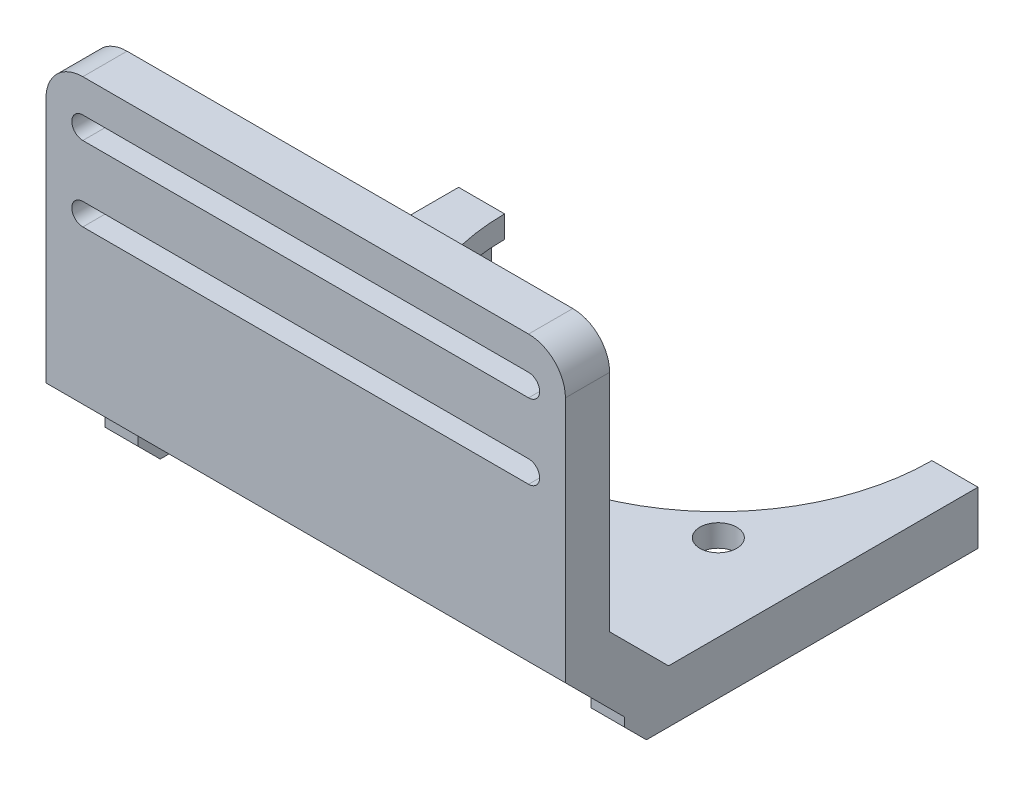
SolidWorks part; units mm, degrees
ref_plane "Front Plane" through (0, 0, 0) normal (0, 0, 1) x (1, 0, 0)
ref_plane "Top Plane" through (0, 0, 0) normal (0, 1, 0) x (1, 0, 0)
ref_plane "Right Plane" through (0, 0, 0) normal (1, 0, 0) x (0, 0, -1)
sketch "Sketch1" plane through (0, 0, 0) normal (0, 0, 1) x (1, 0, 0)
  line L1 (-35.25, 23.25) -> (35.25, 23.25)
  line L2 (-35.25, 23.25) -> (-35.25, -23.25)
  line L3 (-35.25, -23.25) -> (35.25, -23.25)
  line L4 (35.25, 23.25) -> (35.25, -23.25)
  line L5 (-35.25, 23.25) -> (35.25, -23.25) construction
  line L6 (-35.25, -23.25) -> (35.25, 23.25) construction
  point P0 (0, 0)
  dimension "D1" = 70.5
  dimension "D2" = 46.5
extrude "Boss-Extrude1" add sketch "Sketch1" along normal blind 6
sketch "Sketch2" plane through (0, 0, 0) normal (0, 0, -1) x (-1, 0, 0)
  line L0 (35.25, 23.25) -> (35.25, -23.25) construction
  line L1 (-35.25, -23.25) -> (35.25, -23.25)
  line L2 (-35.25, -23.25) -> (-35.25, -20.25)
  line L3 (-35.25, -20.25) -> (35.25, -20.25)
  line L4 (35.25, -23.25) -> (35.25, -20.25)
  dimension "D1" = 3
extrude "Boss-Extrude2" add sketch "Sketch2" along normal blind 50 contours L2 L1 L4 L3
sketch "Sketch3" plane through (0, -20.25, 0) normal (0, 1, 0) x (1, 0, 0)
  line L1 (35.25, 50) -> (-35.25, 50) construction
  circle A1 centre (0, 50) radius 29
  dimension "D1" = 58
extrude "Cut-Extrude1" cut sketch "Sketch3" against normal up to next
sketch "Sketch4" plane through (35.25, 0, 0) normal (1, 0, 0) x (0, 0, -1)
  line L1 (0, -20.25) -> (8, -20.25)
  line L2 (0, -20.25) -> (0, -12.25)
  line L3 (0, -12.25) -> (8, -12.25)
  line L4 (8, -20.25) -> (8, -12.25)
  dimension "D1" = 8
  dimension "D2" = 8
extrude "Boss-Extrude3" add sketch "Sketch4" against normal up to surface (70.5 mm away) up to face at (-35.25, -6.75, -14.6667)
chamfer "Chamfer1" distance 8 angle 45 2 edges at (0, -12.25, -8) (0, -23.25, 6)
sketch "Sketch5" plane through (0, -20.25, 0) normal (0, 1, 0) x (1, 0, 0)
  line L1 (-35.25, 8) -> (35.25, 8) construction
  line L2 (0, 21) -> (0, 8) construction
  line L3 (-29, 50) -> (29, 50) construction
  line L5 (-30.25, 80.25) -> (30.25, 80.25)
  line L6 (-30.25, 80.25) -> (-30.25, 19.75)
  line L7 (-30.25, 19.75) -> (30.25, 19.75)
  line L8 (30.25, 80.25) -> (30.25, 19.75)
  line L9 (-30.25, 80.25) -> (30.25, 19.75) construction
  line L10 (-30.25, 19.75) -> (30.25, 80.25) construction
  circle A0 centre (-23.57, 26.43) radius 2.5
  arc A1 (-29, 50) -> (29, 50) centre (0, 50) ccw construction
  circle A2 centre (23.57, 26.43) radius 2.5
  point P19 (0, 50)
  dimension "D3" = 5
  dimension "D1" = 6.68
  dimension "D2" = 6.68
  dimension "D4" = 60.5
  dimension "D5" = 60.5
extrude "Cut-Extrude2" cut sketch "Sketch5" against normal blind 20 contours A0 | A2
sketch "Sketch6" plane through (0, -23.25, 0) normal (0, -1, 0) x (1, 0, 0)
  line L0 (35.25, -2) -> (-35.25, -2) construction
  line L1 (-35.25, -50) -> (-30.75, -50)
  line L2 (-35.25, -50) -> (-35.25, -2)
  line L3 (-35.25, -2) -> (-30.75, -2)
  line L4 (-30.75, -50) -> (-30.75, -2)
  line L5 (0, 0) -> (0, -21) construction
  line L6 (35.25, -2) -> (30.75, -2)
  line L7 (30.75, -50) -> (30.75, -2)
  line L8 (35.25, -50) -> (30.75, -50)
  line L9 (35.25, -50) -> (35.25, -2)
  arc A0 (29, -50) -> (-29, -50) centre (0, -50) ccw construction
  dimension "D1" = 4.5
extrude "Boss-Extrude4" add sketch "Sketch6" along normal blind 4.2
chamfer "Chamfer2" distance 3 angle 45 2 edges at (-33, -27.45, -2) (33, -27.45, -2)
sketch "Sketch7" plane through (0, 0, 6) normal (0, 0, 1) x (1, 0, 0)
  line L0 (0, 23.25) -> (0, -15.25) construction
  line L1 (35.25, 23.25) -> (-35.25, 23.25) construction
  line L2 (-35.25, -15.25) -> (35.25, -15.25) construction
  line L4 (-30.25, 18.75) -> (30.25, 18.75)
  line L5 (-30.25, 18.75) -> (-30.25, 15.75)
  line L6 (-30.25, 15.75) -> (30.25, 15.75)
  line L7 (30.25, 18.75) -> (30.25, 15.75)
  line L8 (-30.25, 18.75) -> (30.25, 15.75) construction
  line L9 (-30.25, 15.75) -> (30.25, 18.75) construction
  line L13 (-30.25, 8.59) -> (30.25, 8.59)
  line L14 (-30.25, 8.59) -> (-30.25, 5.59)
  line L15 (-30.25, 5.59) -> (30.25, 5.59)
  line L16 (30.25, 8.59) -> (30.25, 5.59)
  line L17 (-30.25, 8.59) -> (30.25, 5.59) construction
  line L18 (-30.25, 5.59) -> (30.25, 8.59) construction
  circle A0 centre (-30.25, 17.25) radius 1.5
  circle A1 centre (30.25, 17.25) radius 1.5
  circle A4 centre (-30.25, 7.09) radius 1.5
  circle A5 centre (30.25, 7.09) radius 1.5
  point P6 (0, 17.25)
  point P16 (0, 7.09)
  dimension "D1" = 3
  dimension "D2" = 60.5
  dimension "D3" = 6
extrude "Cut-Extrude3" cut sketch "Sketch7" against normal up to next contours L5 A0 | L5 A0 | A1 L4 A0 L6 | L14 A4 | L14 A4 | A5 L13 A4 L15 | L7 A1 | L7 A1 | L16 A5 | L16 A5 region at (-29.6134, 17.25, 6) region at (0, 17.25, 6) region at (-30.8866, 17.25, 6) region at (30.8866, 17.25, 6) region at (29.6134, 17.25, 6) region at (-29.6134, 7.09, 6) region at (0, 7.09, 6) region at (-30.8866, 7.09, 6) region at (30.8866, 7.09, 6) region at (29.6134, 7.09, 6)
sketch "Sketch8" plane through (0, 0, 0) normal (0, 0, -1) x (-1, 0, 0)
  line L0 (0, 18.75) -> (0, 15.75) construction
  line L1 (-30.25, 18.75) -> (30.25, 18.75) construction
  line L2 (-30.25, 15.75) -> (30.25, 15.75) construction
  line L3 (-30.25, 8.59) -> (30.25, 8.59)
  line L4 (-30.25, 18.75) -> (30.25, 18.75)
  line L5 (-30.25, 18.75) -> (-30.25, 15.75)
  line L6 (-30.25, 15.75) -> (30.25, 15.75)
  line L7 (30.25, 18.75) -> (30.25, 15.75)
  line L8 (-30.25, 18.75) -> (30.25, 15.75) construction
  line L9 (-30.25, 15.75) -> (30.25, 18.75) construction
  line L10 (-30.25, 8.59) -> (-30.25, 5.59)
  line L11 (-30.25, 5.59) -> (30.25, 5.59)
  line L12 (30.25, 8.59) -> (30.25, 5.59)
  line L13 (0, 8.59) -> (0, 5.59) construction
  line L14 (-30.25, 8.59) -> (30.25, 5.59) construction
  line L15 (-30.25, 5.59) -> (30.25, 8.59) construction
  line L16 (-30.25, 14.5) -> (30.25, 14.5)
  line L17 (-30.25, 4.34) -> (30.25, 4.34)
  line L18 (-30.25, 20) -> (30.25, 20)
  line L19 (-30.25, 9.84) -> (30.25, 9.84)
  circle A0 centre (-30.25, 17.25) radius 1.5
  circle A1 centre (30.25, 17.25) radius 1.5
  circle A2 centre (-30.25, 7.09) radius 1.5
  circle A3 centre (30.25, 7.09) radius 1.5
  circle A4 centre (-30.25, 17.25) radius 2.75
  circle A5 centre (30.25, 17.25) radius 2.75
  circle A6 centre (-30.25, 7.09) radius 2.75
  circle A7 centre (30.25, 7.09) radius 2.75
  point P6 (0, 17.25)
  point P19 (0, 7.09)
  line M13 (-30.25, 18.75) -> (30.25, 18.75)
  arc M14 (30.25, 18.75) -> (30.25, 15.75) centre (30.25, 17.25) cw
  line M15 (30.25, 15.75) -> (-30.25, 15.75)
  arc M16 (-30.25, 15.75) -> (-30.25, 18.75) centre (-30.25, 17.25) cw
  line M17 (-30.25, 8.59) -> (30.25, 8.59)
  arc M18 (30.25, 8.59) -> (30.25, 5.59) centre (30.25, 7.09) cw
  line M19 (30.25, 5.59) -> (-30.25, 5.59)
  dimension "D2" = 1.25
  dimension "D3" = 1.25
  dimension "D1" = 2
extrude "Cut-Extrude4" cut sketch "Sketch8" against normal blind 3 contours A4 L6 M13 M16 | A5 L18 A4 L4 | A5 L6 A4 L16 | A5 M13 M14 M15 | A7 L19 A6 L3 | A7 L11 A6 L17 | A7 M17 M18 M19 | A6 region at (0, 9.2215, 0) region at (-28.9746, 9.4417, 0) region at (0, 4.9585, 0) region at (31.8247, 17.25, 0) region at (0, 19.3815, 0) region at (-28.9746, 19.6017, 0) region at (0, 15.1185, 0)
fillet "Fillet1" radius 5 2 edges at (-35.25, 23.25, 3) (35.25, 23.25, 3)
